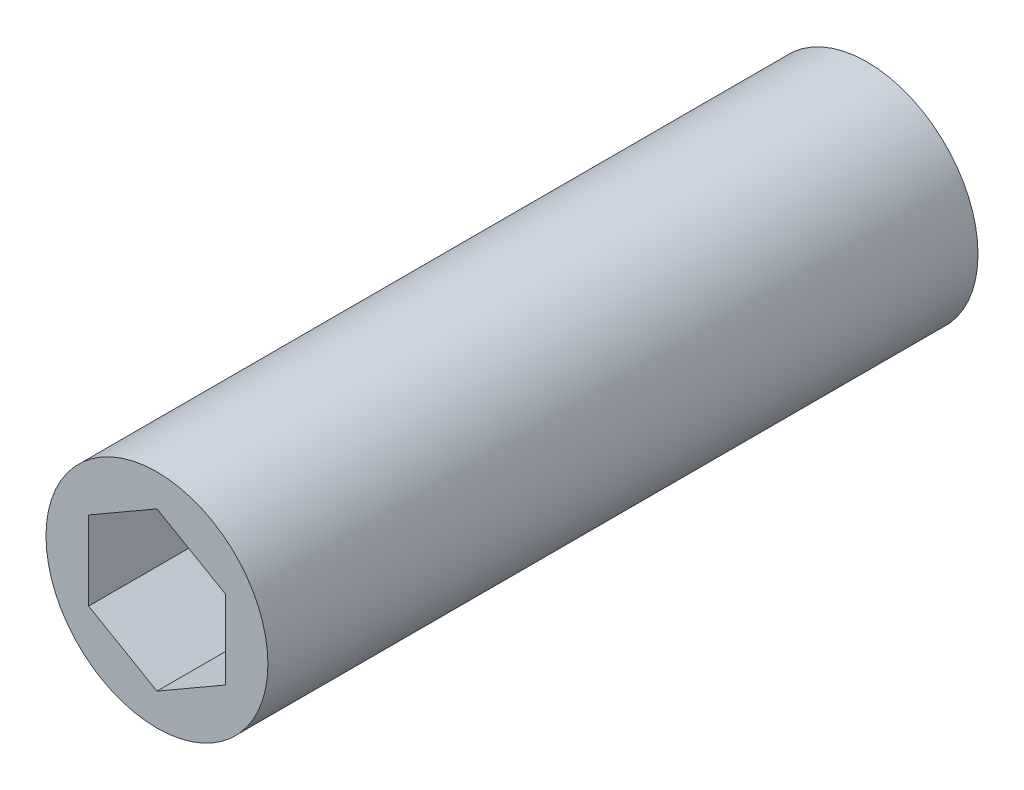
SolidWorks part; units mm, degrees
material "POM Acetal Copolymer"
ref_plane "Front" through (0, 0, 0) normal (0, 0, 1) x (1, 0, 0)
ref_plane "Top" through (0, 0, 0) normal (0, 1, 0) x (1, 0, 0)
ref_plane "Right" through (0, 0, 0) normal (1, 0, 0) x (0, 0, -1)
sketch "Sketch1" plane through (0, 0, 0) normal (0, 0, 1) x (1, 0, 0)
  line L1 (0, 5.6459) -> (-4.8895, 2.823)
  line L2 (-4.8895, 2.823) -> (-4.8895, -2.823)
  line L3 (-4.8895, -2.823) -> (0, -5.6459)
  line L4 (0, -5.6459) -> (4.8895, -2.823)
  line L5 (4.8895, -2.823) -> (4.8895, 2.823)
  line L6 (4.8895, 2.823) -> (0, 5.6459)
  circle A0 centre (0, 0) radius 7.9375
  circle A1 centre (0, 0) radius 4.8895 construction
  dimension "D2" = 15.875
  dimension "D1" = 9.779
extrude "Boss-Extrude1" add sketch "Sketch1" along normal blind 50.8
